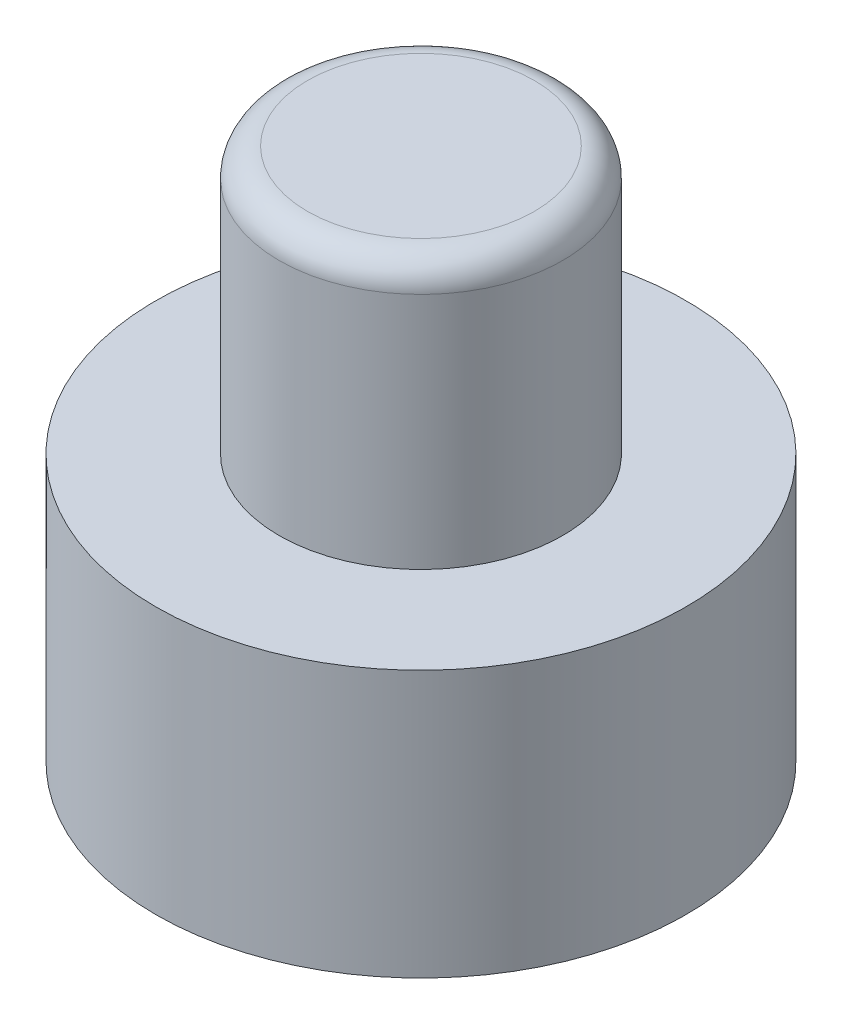
SolidWorks part; units mm, degrees
ref_plane "Front Plane" through (0, 0, 0) normal (0, 0, 1) x (1, 0, 0)
ref_plane "Top Plane" through (0, 0, 0) normal (0, 1, 0) x (1, 0, 0)
ref_plane "Right Plane" through (0, 0, 0) normal (1, 0, 0) x (0, 0, -1)
sketch "Sketch1" plane through (0, 0, 0) normal (0, 1, 0) x (1, 0, 0)
  circle A0 centre (0, 0) radius 4.675
  dimension "D1" = 9.35
extrude "Boss-Extrude1" add sketch "Sketch1" along normal blind 4.7
sketch "Sketch2" plane through (0, 4.7, 0) normal (0, 1, 0) x (1, 0, 0)
  circle A0 centre (0, 0) radius 2.5
  dimension "D1" = 5
extrude "Boss-Extrude2" add sketch "Sketch2" along normal blind 4.7
fillet "Fillet1" radius 0.5 1 edges at (0, 9.4, 2.5)
